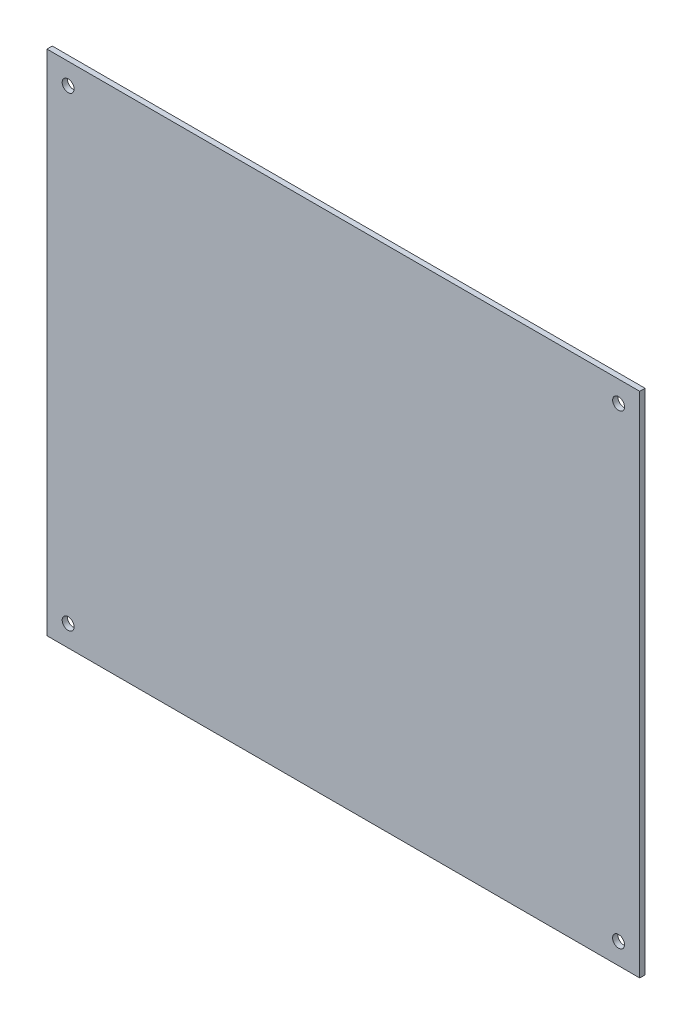
SolidWorks part; units mm, degrees
material "Acrylic (Medium-high impact)"
ref_plane "Front Plane" through (0, 0, 0) normal (0, 0, 1) x (1, 0, 0)
ref_plane "Top Plane" through (0, 0, 0) normal (0, 1, 0) x (1, 0, 0)
ref_plane "Right Plane" through (0, 0, 0) normal (1, 0, 0) x (0, 0, -1)
sketch "Sketch1" plane through (0, 0, 0) normal (0, 0, 1) x (1, 0, 0)
  line L1 (0, 0) -> (355.6, 0)
  line L2 (0, 0) -> (0, -304.8)
  line L3 (0, -304.8) -> (355.6, -304.8)
  line L4 (355.6, 0) -> (355.6, -304.8)
  dimension "D1" = 355.6
  dimension "D2" = 304.8
extrude "Boss-Extrude1" add sketch "Sketch1" along normal blind 3.175
sketch "Sketch2" plane through (0, 0, 3.175) normal (0, 0, 1) x (1, 0, 0)
  line L0 (177.8, 0) -> (177.8, -304.8) construction
  line L1 (355.6, 0) -> (0, 0) construction
  line L2 (0, -304.8) -> (355.6, -304.8) construction
  line L3 (0, -152.4) -> (355.6, -152.4) construction
  line L4 (0, 0) -> (0, -304.8) construction
  line L5 (355.6, -304.8) -> (355.6, 0) construction
  point P0 (12.7, -12.7)
  point P13 (342.9, -12.7)
  point P14 (0, 0)
  point P15 (342.9, -292.1)
  point P16 (12.7, -292.1)
  dimension "D1" = 12.7
  dimension "D2" = 12.7
hole_wizard "1/4 Clearance Hole1" positions "Sketch2" profile "Sketch3" hole size "1/4" standard "ANSI Inch" end condition up to next
sketch "Sketch3" plane through (12.7, -12.7, 3.175) normal (1, 0, 0) x (0, -1, 0)
  line L0 (0, 0) -> (0, 3.175)
  line L1 (0, 3.175) -> (3.5712, 3.175)
  line L2 (3.5712, 3.175) -> (3.5712, 0)
  line L5 (3.5712, 0) -> (0, 0)
  line L11 (0, -6.35) -> (0, 107.95) construction
  dimension "Thru Hole Dia." = 7.1425
  dimension "Thru Hole Depth" = 3.175
